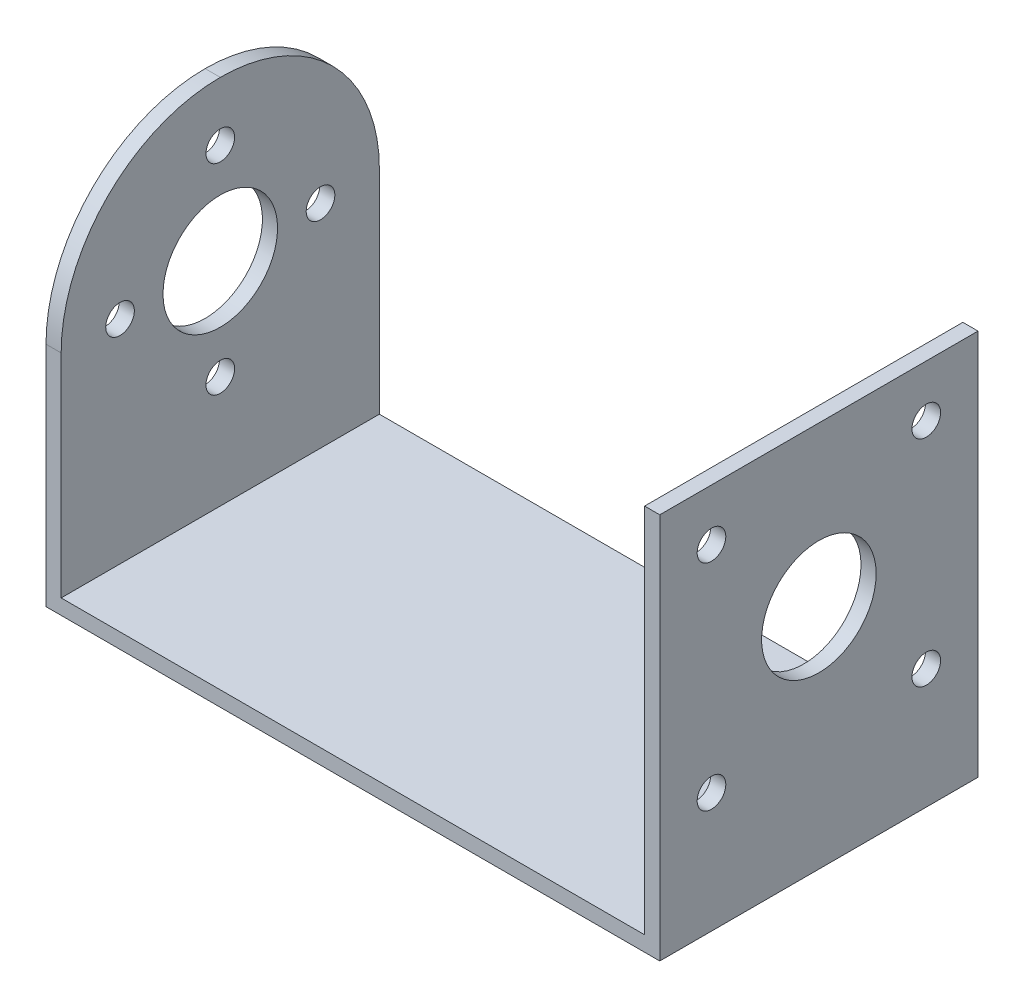
SolidWorks part; units mm, degrees
ref_plane "Front Plane" through (0, 0, 0) normal (0, 0, 1) x (1, 0, 0)
ref_plane "Top Plane" through (0, 0, 0) normal (0, 1, 0) x (1, 0, 0)
ref_plane "Right Plane" through (0, 0, 0) normal (1, 0, 0) x (0, 0, -1)
sketch "Sketch1" plane through (0, 0, 0) normal (0, 0, 1) x (1, 0, 0)
  line L0 (0, 26.9875) -> (0, 0)
  line L1 (0, -55) -> (0, 55) construction
  line L2 (0, 0) -> (42.8625, 0)
  line L3 (55, 0) -> (-55, 0) construction
  line L4 (42.8625, 0) -> (42.8625, 26.9875)
  line L5 (42.8625, 26.9875) -> (41.8042, 26.9875)
  line L6 (41.8042, 26.9875) -> (41.8042, 1.0583)
  line L7 (41.8042, 1.0583) -> (1.0583, 1.0583)
  line L8 (1.0583, 1.0583) -> (1.0583, 26.9875)
  line L9 (1.0583, 26.9875) -> (0, 26.9875)
  dimension "D1" = 42.8625
  dimension "D2" = 1.0583
  dimension "D3" = 1.0583
  dimension "D4" = 26.9875
extrude "Boss-Extrude1" add sketch "Sketch1" along normal blind 22.225
fillet "Fillet1" radius 11.1125 2 edges at (0.5292, 26.9875, 0) (0.5292, 26.9875, 22.225)
sketch "Sketch2" plane through (42.8625, 0, 0) normal (1, 0, 0) x (0, 0, -1)
  line L0 (-22.225, 26.9875) -> (0, 26.9875) construction
  line L1 (-22.225, 26.9875) -> (0, 26.9875) construction
  line L2 (-18.6125, 23.375) -> (-3.6125, 23.375) construction
  line L3 (-18.6125, 8.375) -> (-3.6125, 8.375) construction
  line L4 (-3.6125, 23.375) -> (-18.6125, 8.375) construction
  line L5 (-22.225, 0) -> (0, 0) construction
  circle A0 centre (-3.6125, 23.375) radius 1
  circle A1 centre (-18.6125, 23.375) radius 1
  circle A2 centre (-3.6125, 8.375) radius 1
  circle A3 centre (-18.6125, 8.375) radius 1
  circle A4 centre (-11.1125, 15.875) radius 4
  point P6 (-11.1125, 23.375)
  point P7 (-11.1125, 26.9875)
  point P8 (-11.1125, 8.375)
  dimension "D4" = 2
  dimension "D5" = 8
  dimension "D1" = 15.875
  dimension "D2" = 45
  dimension "D3" = 15
sketch "Sketch3" plane through (0, 0, 0) normal (-1, 0, 0) x (0, 0, 1)
  arc A0 (22.225, 15.875) -> (11.1125, 26.9875) centre (11.1125, 15.875) ccw construction
  arc A1 (22.225, 15.875) -> (11.1125, 26.9875) centre (11.1125, 15.875) ccw construction
  circle A2 centre (11.1125, 15.875) radius 4
  circle A3 centre (11.1125, 15.875) radius 7 construction
  circle A4 centre (11.1125, 22.875) radius 1
  point P16 (11.1125, 15.875)
  dimension "D1" = 8
  dimension "D2" = 14
  dimension "D3" = 2
extrude "Cut-Extrude2" cut sketch "Sketch3" against normal up to surface (1.0583 mm away) up to face at (1.0583, 13.0914, 11.1125)
pattern_circular "CirPattern1" count 4 over 360 about axis through (12.372, 15.875, 11.1125) along (-1, 0, 0) of "Cut-Extrude2"
extrude "Cut-Extrude3" cut sketch "Sketch2" against normal up to surface (1.0583 mm away) up to face at (41.8042, 14.0229, 11.1125)
